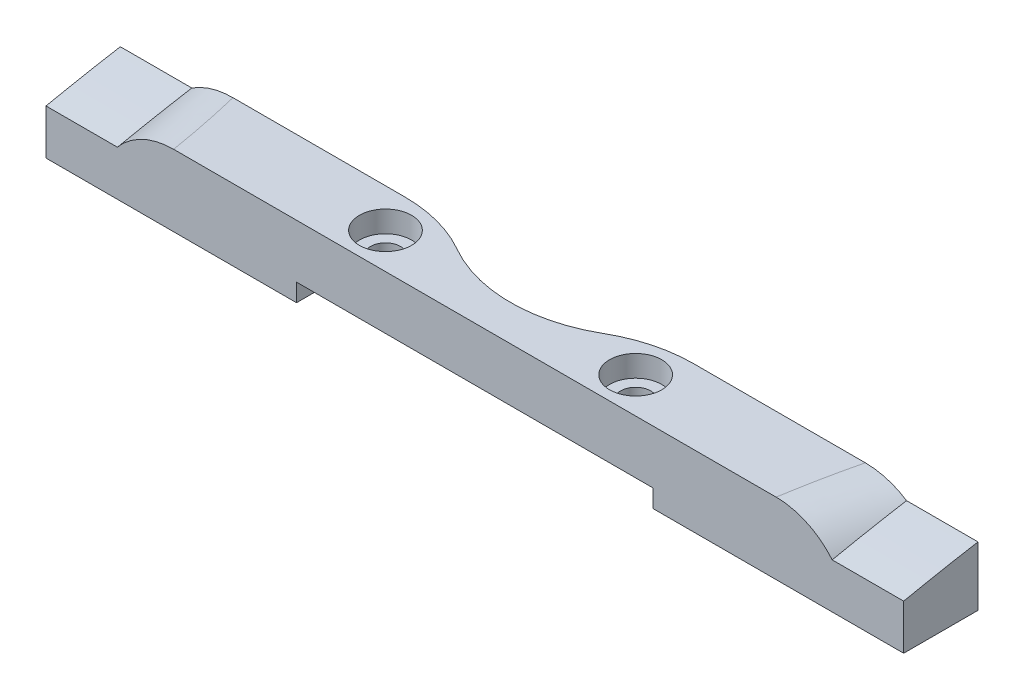
SolidWorks part; units mm, degrees
ref_plane "Ebene vorne" through (0, 0, 0) normal (0, 0, 1) x (1, 0, 0)
ref_plane "Ebene oben" through (0, 0, 0) normal (0, 1, 0) x (1, 0, 0)
ref_plane "Ebene rechts" through (0, 0, 0) normal (1, 0, 0) x (0, 0, -1)
sketch "Skizze1" plane through (0, 0, 0) normal (0, 1, 0) x (1, 0, 0)
  line L0 (-60, 0) -> (60, 0)
  line L1 (60, 0) -> (60, 10.4)
  line L2 (60, 10.4) -> (13.8609, 10.4)
  line L3 (0, 10) -> (0, 0) construction
  line L4 (-60, 0) -> (-60, 10.4)
  line L5 (-13.8609, 10.4) -> (-60, 10.4)
  arc A0 (13.8609, 10.4) -> (0, 5) centre (0, 25.4893) cw
  arc A1 (-13.8609, 10.4) -> (0, 5) centre (0, 25.4893) ccw
  dimension "D3" = 5
  dimension "D1" = 120
  dimension "D2" = 10.4
extrude "Aufsatz-Linear austragen1" add sketch "Skizze1" along normal blind 10
sketch "Skizze3" plane through (0, 10, 0) normal (0, 1, 0) x (1, 0, 0)
  line L0 (0, 0) -> (0, 22.3064) construction
  line L1 (17.5, 5) -> (-17.5, 5) construction
  line L2 (0, 13) -> (0, 5) construction
  circle A0 centre (17.5, 5) radius 2.1
  circle A1 centre (0, 13) radius 2.5 construction
  circle A2 centre (-17.5, 5) radius 2.1
  arc A3 (-13.8609, 10.4) -> (13.8609, 10.4) centre (0, 25.4893) ccw construction
  dimension "D1" = 4.2
  dimension "D4" = 5
  dimension "D2" = 35
  dimension "D3" = 8
  dimension "D5" = 8
extrude "Schnitt-Linear austragen1" cut sketch "Skizze3" against normal blind 10 contours A0 | A2 region at (17.5, 10, -5)
sketch "Skizze4" plane through (-60, 0, 0) normal (1, 0, 0) x (0, 0, -1)
  line L0 (0, 10) -> (10.4, 10)
  line L1 (10.4, 10) -> (10.4, 8.2965)
  line L2 (10.4, 10) -> (10.4, 0) construction
  line L3 (0, 10) -> (0, 6.32)
  line L4 (0, 10) -> (0, 0) construction
  arc A1 (0, 6.32) -> (10.4, 8.2965) centre (58.0172, -270.6068) cw
  point P8 (0, 0)
  point P9 (0, 6.5802)
  point P14 (0, -203.2366)
  point P15 (0, 0)
  point P16 (10.4, -7.3225)
  point P17 (0, 8.1701)
  point P19 (0, 0)
  point P20 (0, 0)
  point P21 (0, 0)
extrude "Schnitt-Linear austragen2" cut sketch "Skizze4" along normal blind 10
fillet "Verrundung1" radius 10 1 edges at (-50, 10, -5.2)
mirror "Spiegeln1" about plane through (0, 0, 0) normal (1, 0, 0) of "Schnitt-Linear austragen2", "Verrundung1"
sketch "Skizze5" plane through (0, 10, 0) normal (0, 1, 0) x (1, 0, 0)
  circle A0 centre (-17.5, 5) radius 3.65
  circle A1 centre (17.5, 5) radius 3.65
  dimension "D1" = 7.3
extrude "Schnitt-Linear austragen3" cut sketch "Skizze5" against normal blind 3
fillet "Verrundung2" radius 20 2 edges at (13.8609, 5, -10.4) (-13.8609, 5, -10.4)
sketch "Skizze6" plane through (0, 0, 0) normal (0, -1, 0) x (1, 0, 0)
  line L1 (-24.9478, 11.0453) -> (24.9478, 11.0453)
  line L2 (-24.9478, 11.0453) -> (-24.9478, -11.0453)
  line L3 (-24.9478, -11.0453) -> (24.9478, -11.0453)
  line L4 (24.9478, 11.0453) -> (24.9478, -11.0453)
  line L5 (-24.9478, 11.0453) -> (24.9478, -11.0453) construction
  line L6 (-24.9478, -11.0453) -> (24.9478, 11.0453) construction
  point P0 (0, 0)
extrude "Schnitt-Linear austragen4" cut sketch "Skizze6" against normal blind 2.5
